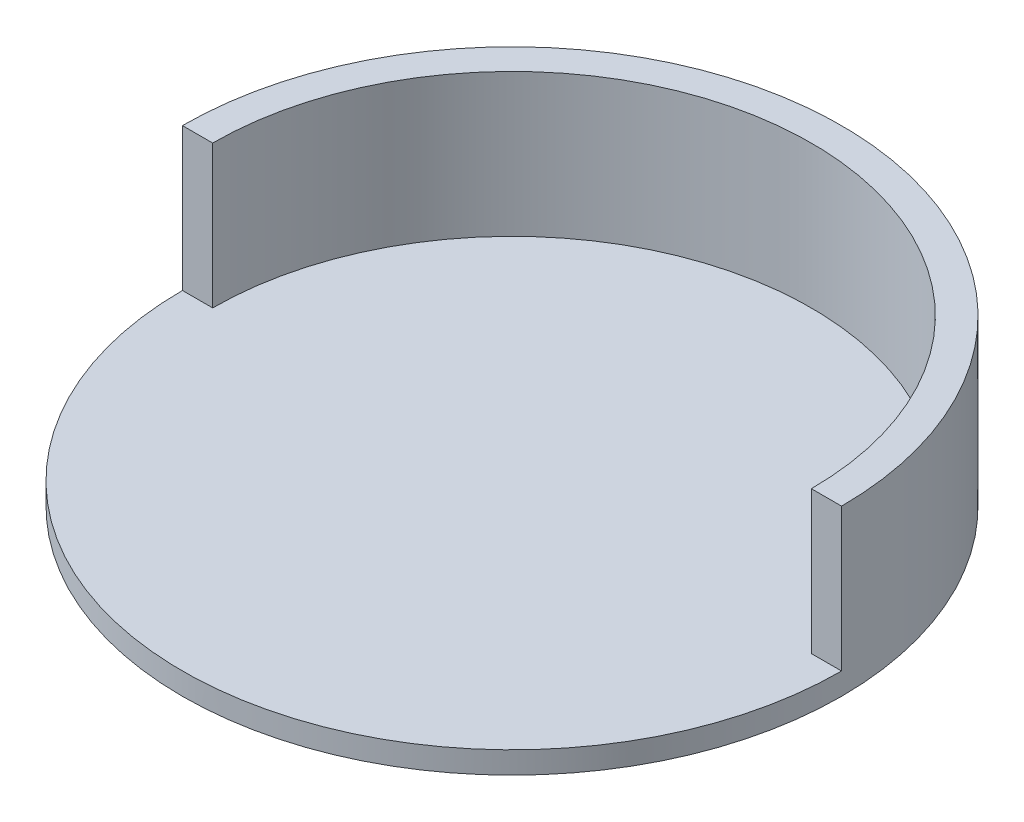
SolidWorks part; units mm, degrees
ref_plane "Front Plane" through (0, 0, 0) normal (0, 0, 1) x (1, 0, 0)
ref_plane "Top Plane" through (0, 0, 0) normal (0, 1, 0) x (1, 0, 0)
ref_plane "Right Plane" through (0, 0, 0) normal (1, 0, 0) x (0, 0, -1)
sketch "Sketch1" plane through (0, 0, 0) normal (0, 1, 0) x (1, 0, 0)
  circle A0 centre (0, 0) radius 30
  dimension "D1" = 60
extrude "Boss-Extrude1" add sketch "Sketch1" along normal blind 2
sketch "Sketch2" plane through (0, 2, 0) normal (0, 1, 0) x (1, 0, 0)
  circle A0 centre (0, 0) radius 27.1
  circle A1 centre (0, 0) radius 27.25
  circle A2 centre (0, 0) radius 32.5
  point P5 (0, 0)
  circle M7 centre (0, 0) radius 30
  dimension "D1" = 54.5
  dimension "D2" = 54.2
extrude "Boss-Extrude2" add sketch "Sketch2" along normal blind 13 contours A0 M7 region at (-29.1515, 2, 0)
sketch "Sketch3" plane through (0, 0, 0) normal (0, -1, 0) x (1, 0, 0)
  circle A5 centre (0, 0) radius 5
  dimension "D1" = 10
extrude "Cut-Extrude2" [suppressed] cut sketch "Sketch3" against normal up to next contours A5
sketch "Sketch5" plane through (0, 0, 0) normal (0, -1, 0) x (1, 0, 0)
  line L1 (-9, -5.5) -> (9, -5.5) construction
  line L2 (-9, -5.5) -> (-9, 5.5) construction
  line L3 (-9, 5.5) -> (9, 5.5) construction
  line L4 (9, -5.5) -> (9, 5.5) construction
  line L5 (-9, -5.5) -> (9, 5.5) construction
  line L6 (-9, 5.5) -> (9, -5.5) construction
  circle A0 centre (9, 5.5) radius 1.3
  circle A1 centre (9, -5.5) radius 1.3
  circle A2 centre (-9, -5.5) radius 1.3
  circle A3 centre (-9, 5.5) radius 1.3
  point P0 (0, 0)
  dimension "D1" = 2.6
  dimension "D2" = 18
  dimension "D3" = 11
extrude "Cut-Extrude3" [suppressed] cut sketch "Sketch5" against normal up to next
sketch "Sketch6" plane through (0, 15, 0) normal (0, 1, 0) x (1, 0, 0)
  line L0 (-55, 0) -> (55, 0) construction
  line L1 (35.8547, 0) -> (-35.5353, 0)
  line L2 (35.8547, 0) -> (35.8547, -35.7749)
  line L3 (35.8547, -35.7749) -> (-35.5353, -35.7749)
  line L4 (-35.5353, 0) -> (-35.5353, -35.7749)
  point P6 (0, 0)
extrude "Cut-Extrude4" cut sketch "Sketch6" against normal up to surface (13 mm away) up to face at (0, 2, 27.25)
